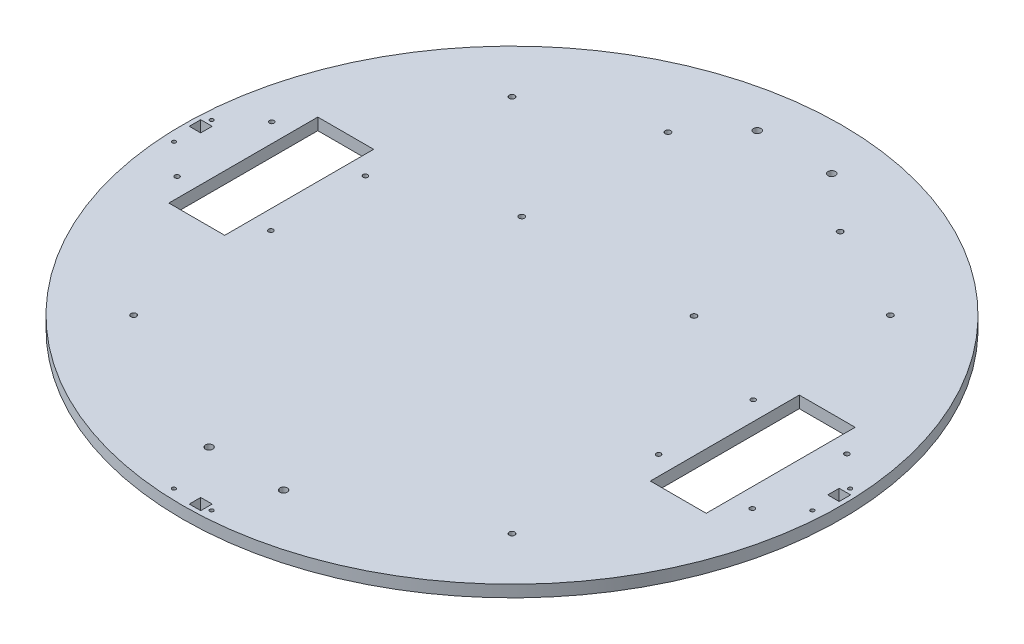
SolidWorks part; units mm, degrees
ref_plane "Front Plane" through (0, 0, 0) normal (0, 0, 1) x (1, 0, 0)
ref_plane "Top Plane" through (0, 0, 0) normal (0, 1, 0) x (1, 0, 0)
ref_plane "Right Plane" through (0, 0, 0) normal (1, 0, 0) x (0, 0, -1)
sketch "Sketch1" plane through (0, 0, 0) normal (0, 1, 0) x (1, 0, 0)
  line L0 (168.375, 7.335) -> (174.525, 7.335)
  line L1 (-144.3, 40) -> (-114.3, 40)
  line L2 (-144.3, 40) -> (-144.3, -40)
  line L3 (-144.3, -40) -> (-114.3, -40)
  line L4 (-114.3, 40) -> (-114.3, -40)
  line L13 (114.3, 40) -> (144.3, 40)
  line L14 (114.3, 40) -> (114.3, -40)
  line L15 (114.3, -40) -> (144.3, -40)
  line L16 (144.3, 40) -> (144.3, -40)
  line L17 (1.185, -168.375) -> (7.335, -168.375)
  line L18 (1.185, -168.375) -> (1.185, -174.525)
  line L19 (1.185, -174.525) -> (7.335, -174.525)
  line L20 (7.335, -168.375) -> (7.335, -174.525)
  line L21 (168.375, 7.335) -> (168.375, 1.185)
  line L22 (168.375, 1.185) -> (174.525, 1.185)
  line L23 (174.525, 7.335) -> (174.525, 1.185)
  line L24 (-174.525, 7.335) -> (-168.375, 7.335)
  line L25 (-174.525, 7.335) -> (-174.525, 1.185)
  line L26 (-174.525, 1.185) -> (-168.375, 1.185)
  line L27 (-168.375, 7.335) -> (-168.375, 1.185)
  circle A0 centre (0, 0) radius 177
  circle A1 centre (-154.46, 25.4) radius 1.27
  circle A2 centre (-154.46, -25.4) radius 1.27
  circle A3 centre (154.46, 25.4) radius 1.27
  circle A4 centre (154.46, -25.4) radius 1.27
  circle A5 centre (-104.14, 25.4) radius 1.27
  circle A6 centre (-104.14, -25.4) radius 1.27
  circle A7 centre (104.14, 25.4) radius 1.27
  circle A8 centre (104.14, -25.4) radius 1.27
  circle A9 centre (-43.25, 127) radius 1.5
  circle A10 centre (49.25, 127) radius 1.5
  circle A11 centre (-43.25, 48.5) radius 1.5
  circle A12 centre (49.25, 48.5) radius 1.5
  circle A13 centre (-101.6, -101.6) radius 1.5
  circle A14 centre (101.6, -101.6) radius 1.5
  circle A15 centre (-101.6, 101.6) radius 1.5
  circle A16 centre (101.6, 101.6) radius 1.5
  circle A17 centre (-20, -142.687) radius 2
  circle A18 centre (20, -142.687) radius 2
  circle A19 centre (-20, 151.7193) radius 2
  circle A20 centre (20, 151.7193) radius 2
  circle A21 centre (-10.125, -171.45) radius 1
  circle A22 centre (10.125, -171.45) radius 1
  circle A23 centre (171.45, -10.125) radius 1
  circle A24 centre (171.45, 10.125) radius 1
  circle A25 centre (-171.45, -10.125) radius 1
  circle A26 centre (-171.45, 10.125) radius 1
  point P9 (-114.3, 0)
  point P10 (-0.9618, 0)
  point P11 (-0.9618, 0)
  point P14 (114.3, 0)
  point P26 (-144.3, 0)
  point P27 (144.3, 0)
  point P73 (173.5253, -9.0763)
  point P74 (0, 0)
  point P75 (173.5253, 10.0633)
  point P76 (181.8999, -8.0275)
  point P77 (0, 0)
  point P78 (0, 0)
  point P79 (0, 0)
  point P80 (0, 0)
  point P89 (0, 0)
  point P90 (0, 0)
  dimension "D1" = 354
  dimension "D10" = 2.54
  dimension "D12" = 10.16
  dimension "D13" = 2.54
  dimension "D16" = 10.16
  dimension "D17" = 50.8
  dimension "D20" = 2.54
  dimension "D22" = 2.54
  dimension "D23" = 10.16
  dimension "D24" = 50.8
  dimension "D25" = 25.4
  dimension "D26" = 2.54
  dimension "D27" = 2.54
  dimension "D32" = 3
  dimension "D33" = 3
  dimension "D34" = 3
  dimension "D35" = 3
  dimension "D44" = 3
  dimension "D45" = 3
  dimension "D46" = 3
  dimension "D47" = 3
  dimension "D55" = 4
  dimension "D56" = 4
  dimension "D59" = 20
  dimension "D60" = 4
  dimension "D61" = 4
  dimension "D62" = 0
  dimension "D63" = 40
  dimension "D64" = 20
  dimension "D65" = 2
  dimension "D66" = 2
  dimension "D74" = 171.45
  dimension "D75" = 2
  dimension "D76" = 2
  dimension "D77" = 0
  dimension "D87" = 2
  dimension "D88" = 2
  dimension "D90" = 2.79
  dimension "D92" = 0
  dimension "D2" = 30
  dimension "D3" = 80
  dimension "D4" = 0
  dimension "D5" = 114.3
  dimension "D6" = 30
  dimension "D7" = 80
  dimension "D8" = 0
  dimension "D9" = 114.3
  dimension "D11" = 50.8
  dimension "D14" = 10.16
  dimension "D15" = 25.4
  dimension "D18" = 25.4
  dimension "D19" = 10.16
  dimension "D21" = 10.16
  dimension "D28" = 50.8
  dimension "D29" = 10.16
  dimension "D30" = 10.16
  dimension "D31" = 25.4
  dimension "D36" = 78.5
  dimension "D37" = 78.5
  dimension "D38" = 92.5
  dimension "D39" = 92.5
  dimension "D40" = 0
  dimension "D41" = 0
  dimension "D42" = 49.25
  dimension "D43" = 127
  dimension "D48" = 203.2
  dimension "D49" = 203.2
  dimension "D50" = 203.2
  dimension "D51" = 203.2
  dimension "D52" = 0
  dimension "D53" = 101.6
  dimension "D54" = 101.6
  dimension "D57" = 40
  dimension "D58" = 0
  dimension "D67" = 0
  dimension "D68" = 20.25
  dimension "D69" = 10.125
  dimension "D70" = 6.15
  dimension "D71" = 6.15
  dimension "D72" = 2.79
  dimension "D73" = 3.075
  dimension "D78" = 20.25
  dimension "D79" = 10.125
  dimension "D80" = 6.15
  dimension "D81" = 6.15
  dimension "D82" = 2.79
  dimension "D83" = 3.075
  dimension "D84" = 171.45
  dimension "D85" = 6.15
  dimension "D86" = 6.15
  dimension "D89" = 20.25
  dimension "D91" = 3.075
  dimension "D93" = 171.45
  dimension "D94" = 10.125
extrude "Boss-Extrude1" add sketch "Sketch1" along normal blind 6.35
